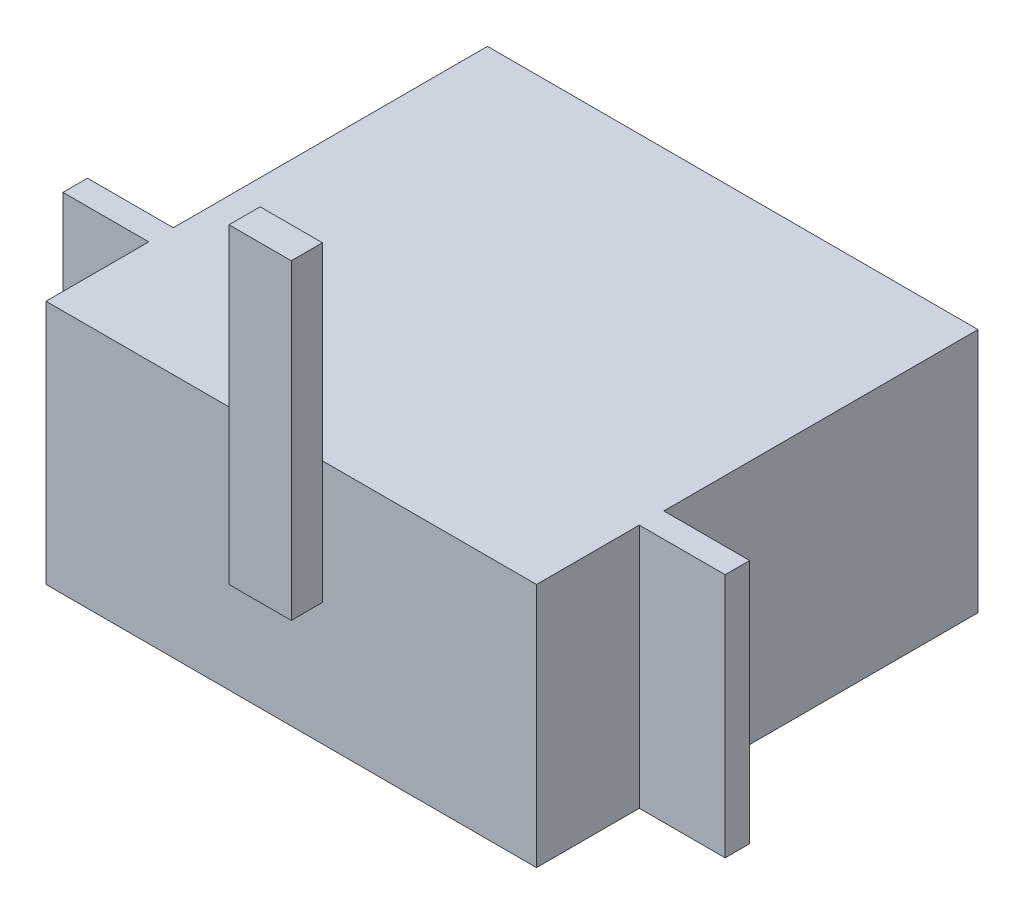
SolidWorks part; units mm, degrees
ref_plane "Front Plane" through (0, 0, 0) normal (0, 0, 1) x (1, 0, 0)
ref_plane "Top Plane" through (0, 0, 0) normal (0, 1, 0) x (1, 0, 0)
ref_plane "Right Plane" through (0, 0, 0) normal (1, 0, 0) x (0, 0, -1)
sketch "Sketch1" plane through (0, 0, 0) normal (0, 1, 0) x (1, 0, 0)
  line L1 (-20, -18) -> (20, -18)
  line L2 (-20, -18) -> (-20, 18)
  line L3 (-20, 18) -> (20, 18)
  line L4 (20, -18) -> (20, 18)
  line L5 (-20, -18) -> (20, 18) construction
  line L6 (-20, 18) -> (20, -18) construction
  point P0 (0, 0)
  dimension "D1" = 40
  dimension "D2" = 36
extrude "Boss-Extrude1" add sketch "Sketch1" along normal mid plane 20
sketch "Sketch2" plane through (0, 0, 0) normal (0, 0, 1) x (1, 0, 0)
  line L0 (-20, -10) -> (20, -10) construction
  line L1 (-20, 10) -> (-27, 10)
  line L2 (-20, 10) -> (-20, -10)
  line L3 (-20, -10) -> (-27, -10)
  line L4 (-27, 10) -> (-27, -10)
  line L5 (20, 10) -> (27, 10)
  line L6 (20, 10) -> (20, -10)
  line L7 (20, -10) -> (27, -10)
  line L8 (27, 10) -> (27, -10)
  dimension "D1" = 7
extrude "Boss-Extrude2" add sketch "Sketch2" along normal blind 2 from offset 7.62
sketch "Sketch3" plane through (0, 0, 0) normal (0, 0, 1) x (1, 0, 0)
  line L0 (19.8, 0) -> (-19.8, 0) construction
  line L1 (-2.54, 0) -> (2.54, 0)
  line L2 (-2.54, 0) -> (-2.54, 25.4)
  line L3 (-2.54, 25.4) -> (2.54, 25.4)
  line L4 (2.54, 0) -> (2.54, 25.4)
  point P6 (0, 25.4)
  dimension "D1" = 5.08
  dimension "D2" = 25.4
extrude "Boss-Extrude3" add sketch "Sketch3" along normal blind 2.54 from surface starting at face at (0, 0, 18)
